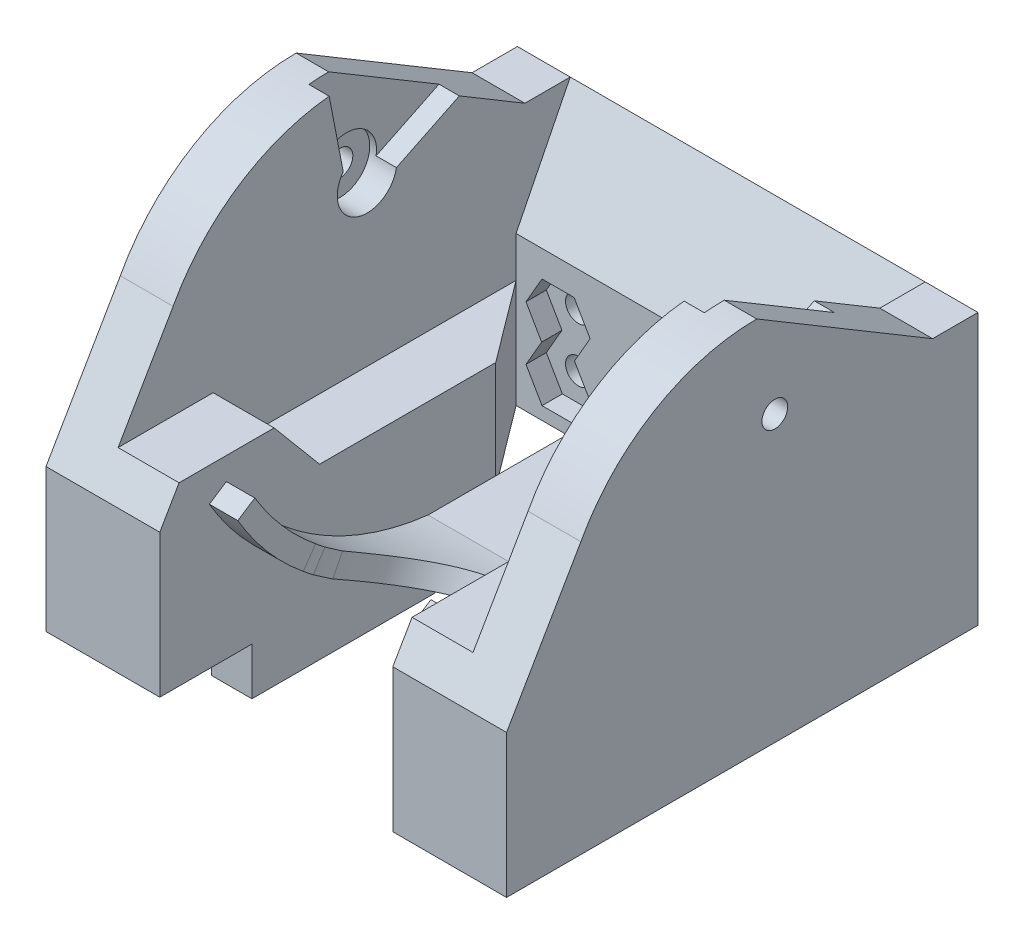
SolidWorks part; units mm, degrees
ref_plane "Alzado" through (0, 0, 0) normal (0, 0, 1) x (1, 0, 0)
ref_plane "Planta" through (0, 0, 0) normal (0, 1, 0) x (1, 0, 0)
ref_plane "Vista lateral" through (0, 0, 0) normal (1, 0, 0) x (0, 0, -1)
sketch "Croquis1" plane through (0, 0, 0) normal (0, 0, 1) x (1, 0, 0)
  line L1 (-48.8873, 14.6225) -> (-14.8873, 14.6225)
  line L2 (-48.8873, 14.6225) -> (-48.8873, -4.3775)
  line L3 (-48.8873, -4.3775) -> (-14.8873, -4.3775)
  line L4 (-14.8873, 14.6225) -> (-14.8873, -4.3775)
  dimension "D1" = 19
  dimension "D2" = 34
extrude "Saliente-Extruir1" add sketch "Croquis1" along normal blind 35
sketch "Croquis2" plane through (0, -4.3775, 0) normal (0, -1, 0) x (1, 0, 0)
  line L0 (-48.8873, 35) -> (-14.8873, 35) construction
  line L1 (-44.9873, 35) -> (-18.7873, 35)
  line L2 (-44.9873, 35) -> (-44.9873, 4)
  line L3 (-44.9873, 4) -> (-18.7873, 4)
  line L4 (-18.7873, 35) -> (-18.7873, 4)
  line L5 (-48.8873, 35) -> (-48.8873, 0) construction
  line L6 (-14.8873, 35) -> (-14.8873, 0) construction
  line L7 (-48.8873, 0) -> (-14.8873, 0) construction
  dimension "D1" = 3.9
  dimension "D2" = 3.9
  dimension "D3" = 26.2
  dimension "D4" = 4
extrude "Cortar-Extruir1" cut sketch "Croquis2" against normal blind 25
sketch "Croquis4" plane through (-18.7873, 0, 0) normal (-1, 0, 0) x (0, 0, 1)
  line L0 (4, 14.6225) -> (4, 6.6225)
  line L1 (4, 14.6225) -> (4, -4.3775) construction
  line L2 (4, 6.6225) -> (0, 14.6225)
  line L3 (0, 14.6225) -> (4, 14.6225)
extrude "Cortar-Extruir3" cut sketch "Croquis4" along normal up to vertex (26.2 mm away) up to point (-44.9873, 14.6225, 4)
sketch "Croquis9" plane through (-14.8873, 0, 0) normal (1, 0, 0) x (0, 0, -1)
  line L0 (-35, 14.6225) -> (0, 14.6225) construction
  line L1 (-29.3158, 14.6225) -> (-3.3495, 14.6225)
  line L7 (-35, -4.3775) -> (0, -4.3775) construction
  arc A0 (-29.3158, 14.6225) -> (-3.3495, 14.6225) centre (-16.3327, 7.6225) cw
  dimension "D2" = 12
extrude "Saliente-Extruir2" add sketch "Croquis9" against normal up to vertex (34 mm away) up to point (-48.8873, 14.6225, 0)
sketch "Croquis10" plane through (0, 14.6225, 0) normal (0, -1, 0) x (1, 0, 0)
  line L1 (-44.9873, 29.3158) -> (-18.7873, 29.3158)
  line L2 (-44.9873, 29.3158) -> (-44.9873, 3.3495)
  line L3 (-44.9873, 3.3495) -> (-18.7873, 3.3495)
  line L4 (-18.7873, 29.3158) -> (-18.7873, 3.3495)
extrude "Cortar-Extruir4" cut sketch "Croquis10" against normal blind 10
sketch "Croquis18" plane through (0, 0, 0) normal (0, 0, -1) x (-1, 0, 0)
  line L0 (48.8873, -4.3775) -> (14.8873, -4.3775) construction
  line L2 (48.8873, 14.6225) -> (48.8873, -4.3775) construction
  circle A0 centre (41.8873, -1.3775) radius 0.95
  circle A1 centre (21.8873, -1.3775) radius 0.95
  circle A2 centre (21.8873, 2.6225) radius 0.95
  circle A3 centre (41.8873, 2.6225) radius 0.95
  dimension "D1" = 3
  dimension "D2" = 7
  dimension "D5" = 4
  dimension "D3" = 2
  dimension "D4" = 2
extrude "Cortar-Extruir11" cut sketch "Croquis18" against normal up to vertex (4 mm away) up to point (-18.7873, -4.3775, 4)
sketch "Croquis19" plane through (0, 0, 4) normal (0, 0, 1) x (1, 0, 0)
  line L0 (-44.2544, -1.3775) -> (-43.0708, -3.4275)
  line L1 (-24.2544, -1.3775) -> (-23.0708, -3.4275)
  line L2 (-23.0708, -3.4275) -> (-20.7037, -3.4275)
  line L3 (-20.7037, -3.4275) -> (-19.5201, -1.3775)
  line L4 (-19.5201, -1.3775) -> (-20.6748, 0.6225)
  line L6 (-23.0997, 0.6225) -> (-24.2544, -1.3775)
  line L7 (-43.0708, -3.4275) -> (-40.7037, -3.4275)
  line L8 (-40.7037, -3.4275) -> (-39.5201, -1.3775)
  line L9 (-39.5201, -1.3775) -> (-40.6748, 0.6225)
  line L11 (-43.0997, 0.6225) -> (-44.2544, -1.3775)
  line L12 (-44.2544, 2.6225) -> (-43.0997, 0.6225)
  line L14 (-40.6748, 0.6225) -> (-39.5201, 2.6225)
  line L15 (-39.5201, 2.6225) -> (-40.7037, 4.6725)
  line L16 (-40.7037, 4.6725) -> (-43.0708, 4.6725)
  line L17 (-43.0708, 4.6725) -> (-44.2544, 2.6225)
  line L18 (-24.2544, 2.6225) -> (-23.0997, 0.6225)
  line L20 (-20.6748, 0.6225) -> (-19.5201, 2.6225)
  line L21 (-19.5201, 2.6225) -> (-20.7037, 4.6725)
  line L22 (-20.7037, 4.6725) -> (-23.0708, 4.6725)
  line L23 (-23.0708, 4.6725) -> (-24.2544, 2.6225)
  line L52 (-20.7037, 0.6725) -> (-23.0708, 0.6725) [skipped]
  line L53 (-23.0708, 0.5725) -> (-20.7037, 0.5725) [skipped]
  line L54 (-43.0708, 0.5725) -> (-40.7037, 0.5725) [skipped]
  circle A0 centre (-21.8873, -1.3775) radius 2.05 construction
  circle A1 centre (-41.8873, -1.3775) radius 2.05 construction
  circle A2 centre (-41.8873, 2.6225) radius 2.05 construction
  circle A3 centre (-21.8873, 2.6225) radius 2.05 construction
  dimension "D2" = 2
  dimension "D3" = 2
extrude "Cortar-Extruir12" cut sketch "Croquis19" against normal blind 1.5
sketch "Croquis21" plane through (-14.8873, 0, 0) normal (1, 0, 0) x (0, 0, -1)
  line L0 (0, -4.3775) -> (0, 14.6225) construction
  line L2 (-35, -4.3775) -> (0, -4.3775) construction
  circle A0 centre (-15, 15.6225) radius 0.95
  dimension "D1" = 15
  dimension "D2" = 20
extrude "Cortar-Extruir14" cut sketch "Croquis21" against normal up to vertex (34 mm away) up to point (-48.8873, 14.6225, 29.3158)
sketch "Croquis23" plane through (0, -4.3775, 0) normal (0, -1, 0) x (1, 0, 0)
  line L0 (-44.9873, 35) -> (-40.4873, 35)
  line L1 (-40.4873, 35) -> (-40.4873, 10)
  line L2 (-40.4873, 10) -> (-44.9873, 4)
  line L3 (-44.9873, 35) -> (-44.9873, 4) construction
  line L4 (-44.9873, 4) -> (-44.9873, 35)
  line L5 (-18.7873, 35) -> (-23.2873, 35)
  line L6 (-23.2873, 35) -> (-23.2873, 10)
  line L7 (-23.2873, 10) -> (-18.7873, 4)
  line L8 (-18.7873, 4) -> (-18.7873, 35)
  dimension "D1" = 25
  dimension "D2" = 25
extrude "Saliente-Extruir3" add sketch "Croquis23" against normal blind 8
sketch "Croquis25" plane through (0, -4.3775, 0) normal (0, -1, 0) x (1, 0, 0)
  line L0 (-40.4873, 35) -> (-43.4873, 35)
  line L1 (-20.2873, 35) -> (-23.2873, 35)
  line L2 (-43.4873, 35) -> (-43.4873, 10)
  line L3 (-43.4873, 10) -> (-40.4873, 10)
  line L4 (-40.4873, 35) -> (-40.4873, 10)
  line L10 (-20.2873, 35) -> (-20.2873, 10)
  line L11 (-20.2873, 10) -> (-23.2873, 10)
  line L12 (-23.2873, 35) -> (-23.2873, 10)
  dimension "D1" = 3
  dimension "D2" = 3
extrude "Saliente-Extruir4" add sketch "Croquis25" along normal blind 3
sketch "Croquis43" plane through (0, 3.6225, 0) normal (0, 1, 0) x (1, 0, 0)
  line L0 (-23.2873, -35) -> (-23.2873, -10) construction
  line L1 (-18.7873, -35) -> (-23.2873, -35)
  line L2 (-18.7873, -35) -> (-18.7873, -23)
  line L3 (-18.7873, -23) -> (-23.2873, -23)
  line L4 (-23.2873, -35) -> (-23.2873, -23)
  line L5 (-44.9873, -35) -> (-44.9873, -4) construction
  line L6 (-40.4873, -35) -> (-44.9873, -35)
  line L7 (-40.4873, -35) -> (-40.4873, -23)
  line L8 (-40.4873, -23) -> (-44.9873, -23)
  line L9 (-44.9873, -35) -> (-44.9873, -23)
  dimension "D1" = 12
  dimension "D2" = 12
extrude "Saliente-Extruir8" add sketch "Croquis43" along normal blind 4
sketch "Croquis27" plane through (-14.8873, 0, 0) normal (1, 0, 0) x (0, 0, -1)
  line L0 (-13.5494, -0.9426) -> (-12.6355, -5.8873)
  line L1 (-33.492, 4.3837) -> (-29.3712, 7.2574)
  arc A2 (-29.3712, 7.2574) -> (-13.5494, -0.9426) centre (-15, 15.6225) ccw
  arc A3 (-33.492, 4.3837) -> (-12.6355, -5.8873) centre (-15, 15.6225) ccw
  dimension "D2" = 21.6395
sketch "Croquis29" plane through (-18.7873, 0, 0) normal (-1, 0, 0) x (0, 0, 1)
  line L0 (17.7974, 22.2996) -> (16.5, 15.6225)
  line L1 (6.2969, 18.4321) -> (13.7431, 14.804)
  arc A0 (6.2969, 18.4321) -> (17.7974, 22.2996) centre (16.3327, 7.6225) cw
  arc A1 (29.3158, 14.6225) -> (3.3495, 14.6225) centre (16.3327, 7.6225) ccw construction
  arc A2 (16.5, 15.6225) -> (13.7431, 14.804) centre (15, 15.6225) cw
extrude "Cortar-Extruir20" cut sketch "Croquis29" against normal blind 1.5
extrude "Cortar-Extruir21" cut sketch "Croquis29<2>" along normal blind 27.7
sketch "Croquis29<2>" plane through (-18.7873, 0, 0) normal (-1, 0, 0) x (0, 0, 1) same geometry as "Croquis29"
sketch "Croquis30" plane through (-48.8873, 0, 0) normal (-1, 0, 0) x (0, 0, 1)
  line L0 (29.3158, 14.6225) -> (35, 4.8278)
  line L1 (35, 14.6225) -> (35, -4.3775) construction
  line L2 (35, 4.8278) -> (35, 14.6225)
  line L3 (35, 14.6225) -> (29.3158, 14.6225)
extrude "Cortar-Extruir22" cut sketch "Croquis30" against normal up to vertex (34 mm away) up to point (-14.8873, 14.6225, 29.3158)
sketch "Croquis35" plane through (0, -4.3775, 0) normal (0, -1, 0) x (1, 0, 0)
  line L0 (-20.2873, 23.2623) -> (-14.8873, 23.2623)
  line L2 (-20.2873, 23.2623) -> (-14.8873, 23.2623) construction
  line L4 (-14.8873, 23.2623) -> (-14.8873, 27.7963)
  line L5 (-14.8873, 35) -> (-14.8873, 0) construction
  line L6 (-14.8873, 27.7963) -> (-20.2873, 23.2623)
sketch "Croquis36" plane through (-18.7873, 0, 0) normal (-1, 0, 0) x (0, 0, 1)
  circle A0 centre (15, 15.6225) radius 2.2
extrude "Cortar-Extruir24" cut sketch "Croquis36" against normal blind 2
extrude "Cortar-Extruir25" cut sketch "Croquis36<2>" along normal blind 28.2
sketch "Croquis36<2>" plane through (-18.7873, 0, 0) normal (-1, 0, 0) x (0, 0, 1) same geometry as "Croquis36"
sketch "Croquis38" plane through (-48.8873, 0, 0) normal (-1, 0, 0) x (0, 0, 1)
  line L0 (3.3495, 14.6225) -> (16.3327, 22.3725)
  line L1 (16.3327, 22.3725) -> (3.3495, 22.3725)
  line L2 (3.3495, 22.3725) -> (3.3495, 14.6225)
  arc A0 (29.3158, 14.6225) -> (3.3495, 14.6225) centre (16.3327, 7.6225) ccw construction
extrude "Cortar-Extruir26" cut sketch "Croquis38" against normal up to vertex (34 mm away) up to point (-14.8873, 14.6225, 29.3158)
sketch "Croquis40" plane through (-48.8873, 0, 0) normal (-1, 0, 0) x (0, 0, 1)
  line L0 (24.4625, 4.9679) -> (27.805, 0.9845)
  line L1 (27.805, 0.9845) -> (27.1921, 0.4702)
  line L2 (27.1921, 0.4702) -> (23.8496, 4.4537)
  line L3 (23.5, 4.1807) -> (26.4826, -0.0789)
  line L4 (26.4826, -0.0789) -> (25.8272, -0.5377)
  line L5 (25.8272, -0.5377) -> (22.8446, 3.7219)
  line L6 (22.4696, 3.4848) -> (25.0696, -1.0186)
  line L7 (24.4625, 4.9679) -> (23.8496, 4.4537)
  line L8 (25.0696, -1.0186) -> (24.3768, -1.4186)
  line L9 (24.3768, -1.4186) -> (21.7768, 3.0848)
  line L10 (22.8446, 3.7219) -> (23.5, 4.1807)
  line L11 (21.3819, 2.8831) -> (23.5795, -1.8297)
  line L12 (23.5795, -1.8297) -> (22.8544, -2.1678)
  line L13 (22.4696, 3.4848) -> (21.7768, 3.0848)
  line L14 (22.8544, -2.1678) -> (20.6568, 2.545)
  line L16 (21.3819, 2.8831) -> (20.6568, 2.545)
  circle A1 centre (15, 15.6225) radius 0.95 construction
  dimension "D2" = 14.2443
  dimension "D3" = 14.248
  dimension "D4" = 14.2464
  dimension "D5" = 0.8
  dimension "D6" = 14.2429
  dimension "D8" = 0.8
  dimension "D9" = 0.8
  dimension "D11" = 0.8
sketch "Croquis41" plane through (-20.2873, 0, 0) normal (1, 0, 0) x (0, 0, -1)
  line L0 (-10, -4.3775) -> (-10, -7.3775)
  line L1 (-10, -7.3775) -> (-10, -4.3775) construction
  line L2 (-10, -7.3775) -> (-13, -7.3775)
  line L3 (-10, -7.3775) -> (-35, -7.3775) construction
  line L4 (-13, -7.3775) -> (-10, -4.3775)
extrude "Cortar-Extruir28" cut sketch "Croquis41" against normal up to vertex (23.2 mm away) up to point (-43.4873, -7.3775, 10)
sketch "Croquis44" plane through (-18.7873, 0, 0) normal (-1, 0, 0) x (0, 0, 1)
  line L0 (23, 7.6225) -> (26.3626, 7.6225)
  line L1 (33.3781, 7.6225) -> (23, 7.6225) construction
  line L2 (26.3626, 7.6225) -> (23, 3.6225)
  line L3 (23, 3.6225) -> (23, 7.6225)
extrude "Cortar-Extruir29" cut sketch "Croquis44" along normal up to vertex (26.2 mm away) up to point (-44.9873, 7.6225, 23)
sketch "Croquis24" plane through (-14.8873, 0, 0) normal (1, 0, 0) x (0, 0, -1)
  line L0 (-15, -3.6275) -> (-15, -5.1273)
  line L1 (-31.1427, 5.1356) -> (-32.3723, 4.2754)
  arc A2 (-31.1427, 5.1356) -> (-15, -3.6275) centre (-15, 15.6225) ccw
  arc A3 (-32.3723, 4.2754) -> (-15, -5.1273) centre (-15, 15.6225) ccw
  dimension "D1" = 19.25
  dimension "D2" = 20.7498
sketch "Croquis45" plane through (-23.2873, 0, 0) normal (-1, 0, 0) x (0, 0, 1)
  line L0 (15, -3.6275) -> (15, -5.1275)
  line L2 (15, -3.6275) -> (15, -5.1273) construction
  line L3 (15, 15.6225) -> (31.1427, 5.1356) construction
  line L4 (15, -3.6275) -> (15, 15.6225) construction
  line L5 (31.1427, 5.1356) -> (29.8848, 5.9527)
  arc A0 (15, -3.6275) -> (31.1427, 5.1356) centre (15, 15.6225) ccw construction
  arc A1 (31.1427, 5.1356) -> (15, -5.1275) centre (13.1536, 15.6036) cw
  arc A4 (15, -3.6275) -> (29.8848, 5.9527) centre (12.6596, 16.3623) ccw
extrude "Saliente-Extruir9" add sketch "Croquis45" along normal up to vertex (17.2 mm away) separate body up to point (-40.4873, -7.3775, 13)
ref_plane "Plano1" through (-31.8873, 4.2754, 32.3723) normal (1, 0, 0) x (0, 0, -1)
sketch "Croquis47" plane through (-31.8873, 4.2754, 32.3723) normal (1, 0, 0) x (0, 0, -1)
  line L0 (17.3723, 11.3471) -> (17.3723, -21.3789) construction
  line L1 (17.3723, 11.3471) -> (0.4676, -24.9052) construction
  line L2 (17.3723, 11.3471) -> (-2.6277, -23.2939) construction
  line L3 (17.3723, 11.3471) -> (-5.5707, -21.419) construction
  line L4 (17.3723, 11.3471) -> (-5.5707, -21.419)
  line L5 (17.3723, 11.3471) -> (-2.6277, -23.2939)
  line L6 (17.3723, 11.3471) -> (0.4676, -24.9052)
  dimension "D1" = 25
  dimension "D2" = 30
  dimension "D3" = 35
ref_plane "Plano2" through (-31.8873, -17.1435, 37.9431) normal (0, -0.8192, 0.5736) x (-1, 0, 0)
sketch "Croquis48" plane through (-31.8873, -17.1435, 37.9431) normal (0, -0.8192, 0.5736) x (-1, 0, 0)
  line L3 (6.5, 0) -> (6.5, -15)
  line L4 (6.5, -15) -> (-6.5, -15)
  line L5 (-6.5, -15) -> (-6.5, 0)
  arc A2 (6.5, 0) -> (-6.5, 0) centre (0, 0) ccw
ref_plane "Plano3" through (-31.8873, -19.0185, 35) normal (0, -0.866, 0.5) x (-1, 0, 0)
ref_plane "Plano4" through (-31.8873, -20.6298, 31.9047) normal (0, -0.9063, 0.4226) x (-1, 0, 0)
sketch "Croquis49" plane through (-31.8873, -19.0185, 35) normal (0, -0.866, 0.5) x (-1, 0, 0)
  circle A0 centre (0, 0) radius 6.5
sketch "Croquis50" plane through (-31.8873, -20.6298, 31.9047) normal (0, -0.9063, 0.4226) x (-1, 0, 0)
  circle A0 centre (0, 0) radius 6.5
sweep "Cortar-Barrer2" cut profiles "Croquis48" path "Croquis47"
sketch "Croquis51" plane through (-31.8873, 4.2754, 32.3723) normal (1, 0, 0) x (0, 0, -1)
  line L0 (17.3723, 11.3471) -> (-2.6277, -23.2939)
sweep "Cortar-Barrer3" cut profiles "Croquis49" path "Croquis51"
sketch "Croquis52" plane through (-31.8873, 4.2754, 32.3723) normal (1, 0, 0) x (0, 0, -1)
  line L0 (17.3723, 11.3471) -> (0.4676, -24.9052)
sweep "Cortar-Barrer4" cut profiles "Croquis50" path "Croquis52"
sketch "Croquis56" plane through (0, 0, 35) normal (0, 0, 1) x (1, 0, 0)
  line L0 (-23.2873, -7.3775) -> (-20.2873, -7.3775)
  line L1 (-20.2873, -7.3775) -> (-20.2873, -4.3775)
  line L2 (-20.2873, -4.3775) -> (-14.8873, -4.3775)
  line L3 (-14.8873, -4.3775) -> (-14.8873, 4.8278)
  line L4 (-14.8873, 4.8278) -> (-23.2873, 4.8278)
  line L5 (-23.2873, 4.8278) -> (-23.2873, -7.3775)
  line L6 (-40.4873, -7.3775) -> (-40.4873, 4.8278)
  line L7 (-40.4873, 4.8278) -> (-48.8873, 4.8278)
  line L8 (-48.8873, 4.8278) -> (-48.8873, -4.3775)
  line L9 (-48.8873, -4.3775) -> (-43.4873, -4.3775)
  line L10 (-43.4873, -4.3775) -> (-43.4873, -7.3775)
  line L11 (-43.4873, -7.3775) -> (-40.4873, -7.3775)
extrude "Saliente-Extruir15" add sketch "Croquis56" along normal blind 2
sketch "Croquis58" plane through (0, 0, 37) normal (0, 0, 1) x (1, 0, 0)
  line L0 (-40.4873, -7.3775) -> (-40.4873, 4.8278) construction
  line L2 (-40.4873, -1.2748) -> (-40.4873, 6.807)
  line L3 (-40.4873, 6.807) -> (-23.2873, 6.807)
  line L4 (-23.2873, -1.2748) -> (-23.2873, 6.807)
  line L5 (-23.2873, -1.2748) -> (-23.2873, -3.2748)
  line L6 (-23.2873, 4.8278) -> (-23.2873, -7.3775) construction
  line L7 (-23.2873, -3.2748) -> (-40.4873, -3.2748)
  line L8 (-40.4873, -3.2748) -> (-40.4873, -1.2748)
sketch "Croquis60" plane through (0, -4.3775, 0) normal (0, -1, 0) x (1, 0, 0)
  line L1 (-48.8873, 35) -> (-48.8873, 0)
  line L2 (-43.4873, 35) -> (-43.4873, 10)
  line L3 (-43.4873, 10) -> (-48.8873, 0)
  line L4 (-14.8873, 0) -> (-14.8873, 37)
  line L5 (-14.8873, 37) -> (-20.2873, 37)
  line L6 (-20.2873, 37) -> (-20.2873, 10)
  line L7 (-20.2873, 10) -> (-14.8873, 0)
  line L9 (-48.8873, 35) -> (-48.8873, 37)
  line L10 (-48.8873, 37) -> (-43.4873, 37)
  line L11 (-43.4873, 37) -> (-43.4873, 35)
extrude "Saliente-Extruir30" add sketch "Croquis60" along normal blind 1
sketch "Croquis61" plane through (0, 0, 15) normal (0, 0, -1) x (-1, 0, 0)
  line L0 (23.2873, -3.6275) -> (23.2873, -5.1275) construction
  line L1 (40.4873, -5.1275) -> (23.2873, -5.1275)
  line L2 (40.4873, -5.1275) -> (40.4873, -3.6275)
  line L3 (40.4873, -3.6275) -> (23.2873, -3.6275)
  line L4 (23.2873, -5.1275) -> (23.2873, -3.6275)
  line L5 (40.4873, -3.6275) -> (23.2873, -3.6275) construction
extrude "Saliente-Extruir31" add sketch "Croquis61" along normal up to vertex (11 mm away) up to point (-18.7873, -4.3775, 4)
sketch "Croquis62" plane through (-23.2873, 0, 0) normal (1, 0, 0) x (0, 0, -1)
  line L0 (-4, -4.3775) -> (-4, -5.1275)
  line L1 (-4, -5.1275) -> (0, -4.3775)
  line L2 (0, -4.3775) -> (-4, -4.3775)
extrude "Saliente-Extruir32" add sketch "Croquis62" against normal up to vertex (17.2 mm away) up to point (-40.4873, -5.1275, 4)
sketch "Croquis63" plane through (0, -7.3775, 0) normal (0, -1, 0) x (1, 0, 0)
  line L0 (-43.4873, 37) -> (-43.4873, 13) construction
  line L1 (-40.4873, 13) -> (-43.4873, 13)
  line L2 (-40.4873, 13) -> (-40.4873, 28)
  line L3 (-40.4873, 28) -> (-43.4873, 28)
  line L4 (-43.4873, 13) -> (-43.4873, 28)
  line L5 (-23.2873, 37) -> (-23.2873, 13) construction
  line L6 (-20.2873, 13) -> (-23.2873, 13)
  line L7 (-20.2873, 13) -> (-20.2873, 28)
  line L8 (-20.2873, 28) -> (-23.2873, 28)
  line L9 (-23.2873, 13) -> (-23.2873, 28)
  dimension "D1" = 15
extrude "Saliente-Extruir33" add sketch "Croquis63" along normal blind 1.5
sketch "Croquis64" plane through (0, -7.3775, 0) normal (0, -1, 0) x (1, 0, 0)
  line L1 (-43.4873, 37) -> (-20.2873, 37)
  line L2 (-43.4873, 37) -> (-43.4873, 28)
  line L3 (-43.4873, 28) -> (-20.2873, 28)
  line L4 (-20.2873, 37) -> (-20.2873, 28)
extrude "Cortar-Extruir30" cut sketch "Croquis64" against normal up to vertex (2 mm away) up to point (-14.8873, -5.3775, 37)
sketch "Croquis65" plane through (-43.4873, 0, 0) normal (-1, 0, 0) x (0, 0, 1)
  line L0 (13, -7.3775) -> (14.5, -8.8775)
  line L1 (28, -8.8775) -> (13, -8.8775) construction
  line L2 (14.5, -8.8775) -> (13, -8.8775)
  line L3 (13, -8.8775) -> (13, -7.3775)
extrude "Cortar-Extruir31" cut sketch "Croquis65" against normal up to vertex (23.2 mm away) up to point (-20.2873, -8.8775, 13)
sketch "Croquis67" plane through (0, 0, 37) normal (0, 0, 1) x (1, 0, 0)
  line L13 (-48.8873, -5.3775) -> (-14.8873, -5.3775)
  line L14 (-48.8873, -5.3775) -> (-48.8873, 6.0954)
  line L15 (-48.8873, 6.0954) -> (-14.8873, 6.0954)
  line L16 (-14.8873, -5.3775) -> (-14.8873, 6.0954)
extrude "Cortar-Extruir32" cut sketch "Croquis67" against normal blind 2.2
